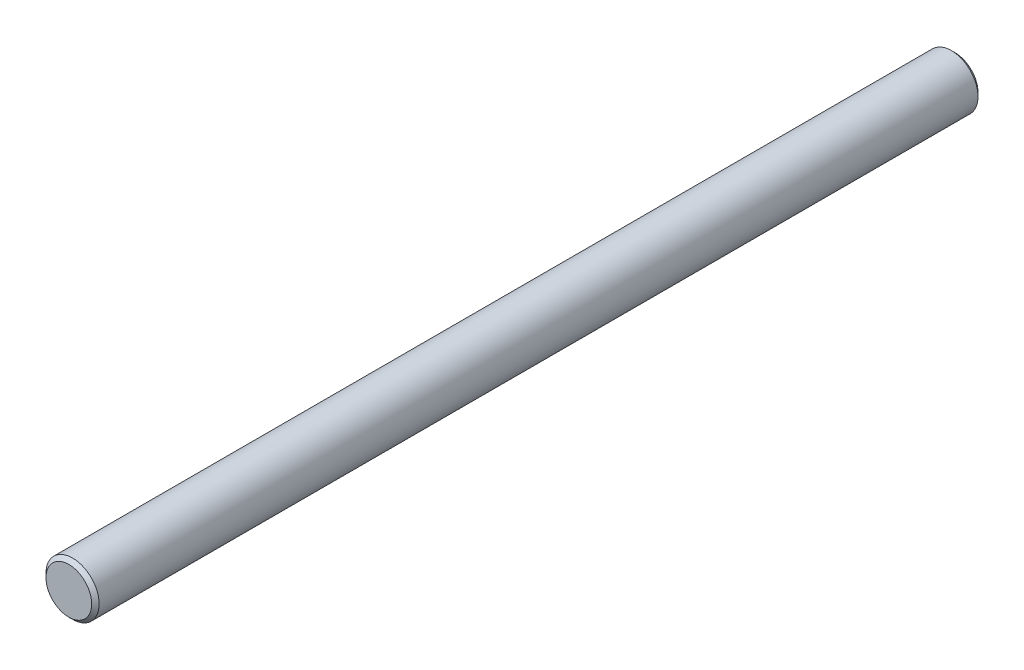
SolidWorks part; units mm, degrees
ref_plane "Front Plane" through (0, 0, 0) normal (0, 0, 1) x (1, 0, 0)
ref_plane "Top Plane" through (0, 0, 0) normal (0, 1, 0) x (1, 0, 0)
ref_plane "Right Plane" through (0, 0, 0) normal (1, 0, 0) x (0, 0, -1)
sketch "Sketch1" plane through (0, 0, 0) normal (0, 0, 1) x (1, 0, 0)
  line L0 (-3, 0) -> (3, 0) construction
  line L5 (0, 3) -> (0, -3) construction
  circle A1 centre (0, 0) radius 3
  point P7 (-3, 0)
  point P8 (3, 0)
  point P12 (0, -3)
  point P13 (0, 3)
  dimension "Diameter" = 6
sketch "Sketch2" plane through (0, 0, 0) normal (1, 0, 0) x (0, 0, -1)
  line L0 (-44, -3) -> (-44, 3) construction
  line L1 (50, -3) -> (-50, -3)
  line L2 (50, -3) -> (50, 3)
  line L3 (50, 3) -> (-50, 3)
  line L4 (-50, -3) -> (-50, 3)
  line L5 (50, -3) -> (-50, 3) construction
  line L6 (50, 3) -> (-50, -3) construction
  line L7 (44, -3) -> (44, 3) construction
  line L8 (-50, 2.58) -> (-49.58, 3) construction
  point P0 (0, 0)
  point P8 (-50, 3)
  point P9 (50, 3)
  point P14 (-44, 3)
  point P15 (-44, -3)
  point P16 (44, 3)
  point P17 (44, -3)
  point P25 (0, -3)
  dimension "Length" = 100
  dimension "D1" = 6
  dimension "D2" = 6
  dimension "Chamfer Typ," = 45
  dimension "D4" = 0.42
sketch "Sketch3" plane through (0, 0, 0) normal (0, 0, 1) x (1, 0, 0)
  circle A0 centre (0, 0) radius 3 construction
  circle A1 centre (0, 0) radius 3
extrude "Boss-Extrude1" add sketch "Sketch3" along normal up to vertex (50 mm away) and the other way up to vertex (50 mm away) up to point (0, 3, 50) other way up to point (0, 3, -50)
chamfer "Chamfer1" distance 0.42 angle 45 2 edges at (3, 0, -50) (3, 0, 50)
equation "\"D1@Sketch2\"=\"Diameter@Sketch1\""
equation "\"D2@Sketch2\"=\"Diameter@Sketch1\""
equation "\"D1@Chamfer1\"=\"Diameter@Sketch1\"*.07"
equation "\"D4@Sketch2\"=\"Diameter@Sketch1\"*.07"
equation "\"D2@Chamfer1\"=\"Chamfer Typ,@Sketch2\""
